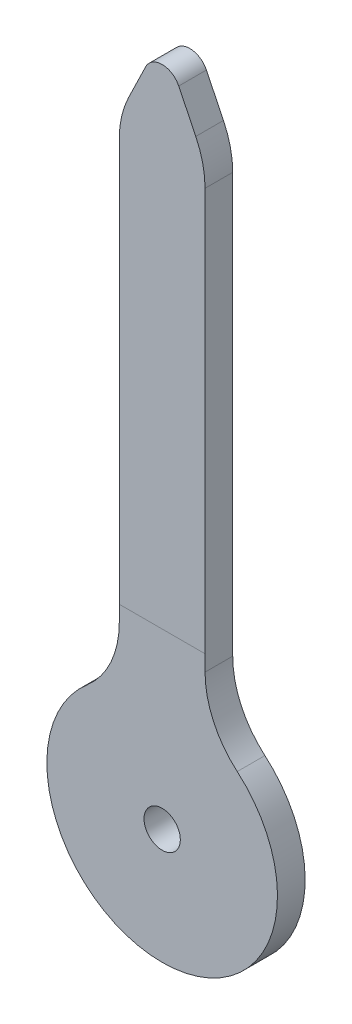
SolidWorks part; units mm, degrees
material "Acrylic (Medium-high impact)"
ref_plane "Front Plane" through (0, 0, 0) normal (0, 0, 1) x (1, 0, 0)
ref_plane "Top Plane" through (0, 0, 0) normal (0, 1, 0) x (1, 0, 0)
ref_plane "Right Plane" through (0, 0, 0) normal (1, 0, 0) x (0, 0, -1)
sketch "Sketch1" plane through (0, 0, 0) normal (0, 0, 1) x (1, 0, 0)
  line L0 (0, 0) -> (0, 18.2372) construction
  line L1 (-0.3175, 18.2372) -> (0.3175, 18.2372)
  line L7 (1.1811, 2.9471) -> (1.1811, 16.4592)
  line L8 (-1.1811, 2.9471) -> (-1.1811, 16.4592)
  line L9 (-1.1811, 0) -> (-1.1811, 18.2372) construction
  line L10 (1.1811, 0) -> (1.1811, 18.2372) construction
  line L11 (-1.1811, 16.4592) -> (-0.3175, 18.2372)
  line L13 (1.1811, 16.4592) -> (0.3175, 18.2372)
  circle A0 centre (0, 0) radius 0.5
  arc A3 (-1.1811, 2.9471) -> (1.1811, 2.9471) centre (0, 0) ccw
  point P6 (0, 18.2372)
  dimension "D1" = 1.778
  dimension "D2" = 6.35
  dimension "D5" = 1
  dimension "D3" = 18.2372
  dimension "D4" = 0.3175
  dimension "D8" = 1.1811
extrude "Boss-Extrude1" add sketch "Sketch1" along normal blind 0.762
sketch "Sketch2" plane through (0, 0, 0.762) normal (0, 0, 1) x (1, 0, 0)
  line L0 (-1.1811, 4.7752) -> (1.1811, 4.7752)
  line L1 (-1.1811, 16.4592) -> (-1.1811, 2.9471) construction
  line L2 (1.1811, 2.9471) -> (1.1811, 16.4592) construction
  dimension "D1" = 4.7752
split line "Split Line1"
fillet "Fillet1" radius 2.54 4 edges at (-1.1811, 2.9471, 0.381) (1.1811, 2.9471, 0.381) (1.1811, 16.4592, 0.381) (-1.1811, 16.4592, 0.381)
fillet "Fillet2" 2 edges at (0.3175, 18.2372, 0.381) (-0.3175, 18.2372, 0.381) type full round first side face at (0.6217, 17.611, 0.381) second side face at (-0.6217, 17.611, 0.381) middle face at (0, 18.2372, 0.381)
